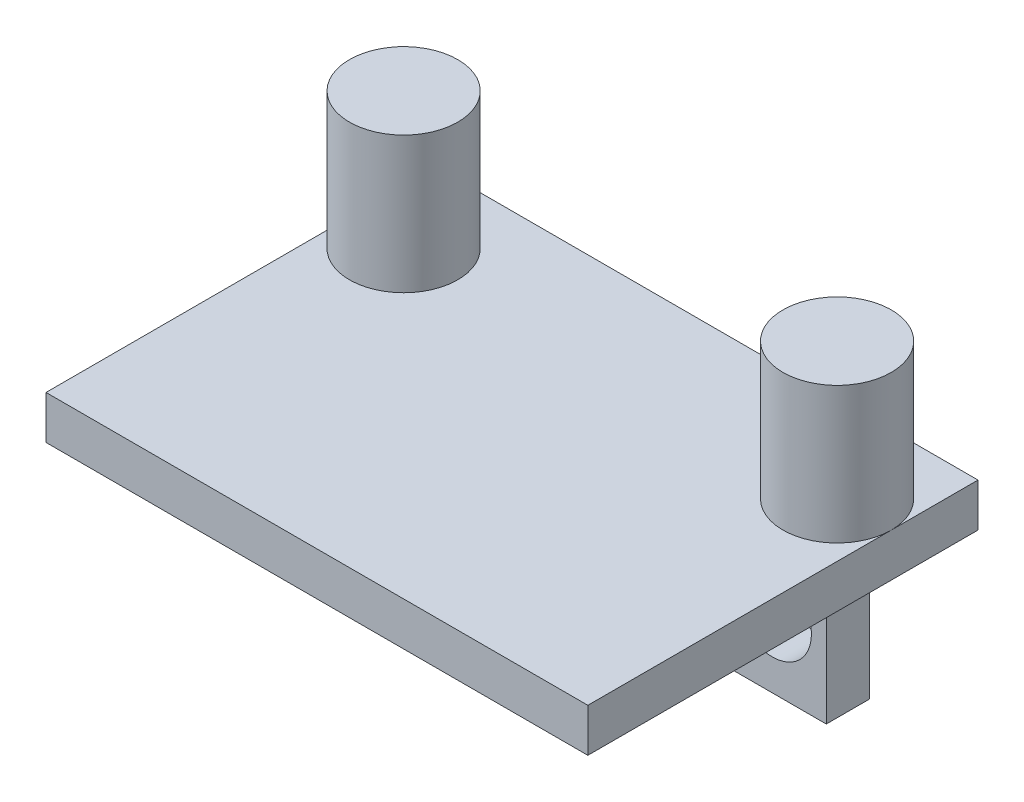
SolidWorks part; units mm, degrees
ref_plane "Front Plane" through (0, 0, 0) normal (0, 0, 1) x (1, 0, 0)
ref_plane "Top Plane" through (0, 0, 0) normal (0, 1, 0) x (1, 0, 0)
ref_plane "Right Plane" through (0, 0, 0) normal (1, 0, 0) x (0, 0, -1)
sketch "Sketch1" plane through (0, 0, 0) normal (1, 0, 0) x (0, 0, -1)
  line L0 (16.6989, -1.875) -> (-15.3011, -1.875)
  line L1 (-15.3011, -1.875) -> (-15.3011, -5.875)
  line L12 (-15.3011, -5.875) -> (-6.3011, -5.875)
  line L13 (-6.3011, -5.875) -> (-5.3011, -6.675)
  line L14 (-5.3011, -6.675) -> (6.1989, -6.675)
  line L15 (6.1989, -6.675) -> (7.1989, -5.875)
  line L16 (7.1989, -5.875) -> (16.1989, -5.875)
  line L17 (16.1989, -5.875) -> (17.6989, -6.875)
  line L18 (17.6989, -6.875) -> (17.6989, -12.375)
  line L19 (17.6989, -12.375) -> (16.6989, -13.375)
  line L20 (16.6989, -13.375) -> (16.6989, -24.375)
  line L21 (16.6989, -24.375) -> (20.6989, -24.375)
  line L22 (20.6989, -24.375) -> (20.6989, -1.875)
  line L23 (20.6989, -1.875) -> (16.6989, -1.875)
  dimension "D1" = 9
  dimension "D2" = 9
  dimension "D3" = 11.5
  dimension "D4" = 0.8
  dimension "D5" = 0.8
  dimension "D6" = 1
  dimension "D7" = 1
  dimension "D8" = 1.5
  dimension "D9" = 1
  dimension "D10" = 5.5
  dimension "D11" = 1
  dimension "D12" = 4
  dimension "D13" = 11
extrude "Boss-Extrude1" add sketch "Sketch1" along normal blind 30 contours L0 L1 L12 L13 L14 L15 L16 L17 L18 L19 L20 L21 L22 L23
sketch "Sketch2" plane through (0, 0, -20.6989) normal (0, 0, -1) x (-1, 0, 0)
  line L0 (-30, -13.375) -> (0, -13.375) construction
  line L1 (0, -13.375) -> (-30, -24.375) construction
  line L2 (-30, -24.375) -> (0, -24.375) construction
  line L3 (0, -24.375) -> (-30, -13.375) construction
  line L4 (-30, -17.875) -> (0, -17.875) construction
  line L5 (-30, -24.375) -> (-30, -1.875) construction
  line L6 (0, -24.375) -> (0, -1.875) construction
  line L7 (-15, -18.875) -> (-15, -13.375) construction
  circle A0 centre (-25, -17.875) radius 3.625
  circle A1 centre (-5, -17.875) radius 3.625
  dimension "D1" = 7.25
  dimension "D2" = 10
extrude "Cut-Extrude1" cut sketch "Sketch2" against normal through all
sketch "Sketch3" plane through (0, 0, 0) normal (-1, 0, 0) x (0, 0, 1)
  line L0 (-20.6989, -24.375) -> (-20.6989, -1.875) construction
  line L1 (15.3011, -1.875) -> (-20.6989, -1.875)
  line L2 (15.3011, -1.875) -> (15.3011, -5.8728)
  line L3 (15.3011, -5.8728) -> (-20.6989, -5.8728)
  line L4 (-20.6989, -1.875) -> (-20.6989, -5.8728)
extrude "Boss-Extrude2" add sketch "Sketch3" along normal blind 10
sketch "Sketch4" plane through (30, 0, 0) normal (1, 0, 0) x (0, 0, -1)
  line L1 (-15.3011, -5.875) -> (20.6989, -5.875)
  line L2 (-15.3011, -5.875) -> (-15.3011, -1.875)
  line L3 (-15.3011, -1.875) -> (20.6989, -1.875)
  line L4 (20.6989, -5.875) -> (20.6989, -1.875)
extrude "Boss-Extrude3" add sketch "Sketch4" along normal blind 10
sketch "Sketch5" plane through (0, -1.875, 0) normal (0, 1, 0) x (1, 0, 0)
  line L0 (-10, 2.6989) -> (40, 2.6989) construction
  line L1 (-10, -15.3011) -> (-10, 20.6989) construction
  line L2 (40, 20.6989) -> (40, -15.3011) construction
  line L3 (15, 20.6989) -> (15, -15.3011) construction
  line L4 (40, 20.6989) -> (-10, 20.6989) construction
  line L5 (40, -15.3011) -> (-10, -15.3011) construction
  circle A0 centre (35, 12.6989) radius 5
  circle A1 centre (-5, 12.6989) radius 5
  dimension "D1" = 10
  dimension "D2" = 10
  dimension "D3" = 5
extrude "Boss-Extrude4" add sketch "Sketch5" along normal blind 12.6 contours A1 | A0
